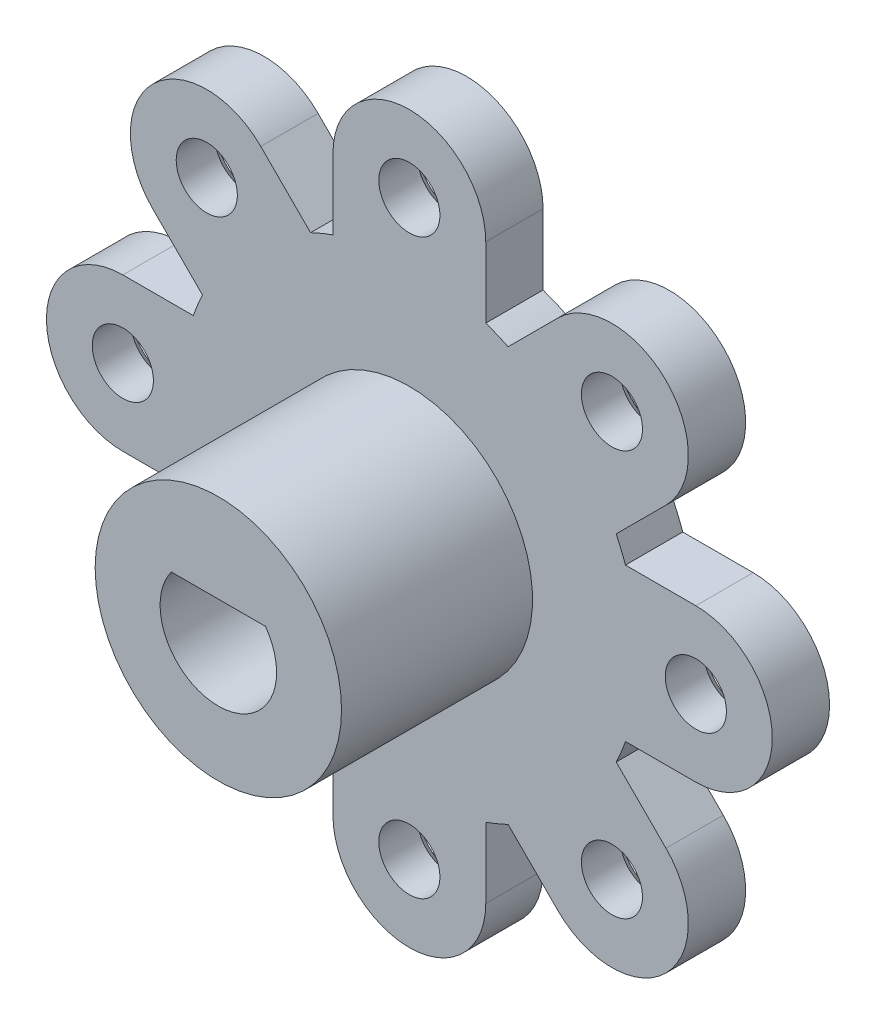
SolidWorks part; units mm, degrees
ref_plane "Front Plane" through (0, 0, 0) normal (0, 0, 1) x (1, 0, 0)
ref_plane "Top Plane" through (0, 0, 0) normal (0, 1, 0) x (1, 0, 0)
ref_plane "Right Plane" through (0, 0, 0) normal (1, 0, 0) x (0, 0, -1)
ref_axis "Axe1" through (0, 0, 11.8837) along (0, 0, -1)
sketch "Esquisse1" plane through (0, 0, 0) normal (0, 0, 1) x (1, 0, 0)
  line L0 (11.3137, 4) -> (15, 4)
  line L1 (11.3137, -4) -> (15, -4)
  line L2 (0, 0) -> (11.0866, 4.5922)
  line L3 (0, 0) -> (11.0866, -4.5922)
  line L4 (0, 0) -> (15, 0) construction
  arc A0 (11.0866, 4.5922) -> (11.3137, 4) centre (0, 0) cw
  arc A1 (11.0866, -4.5922) -> (11.3137, -4) centre (0, 0) ccw
  arc A2 (15, -4) -> (15, 4) centre (15, 0) ccw
  dimension "D1" = 12
  dimension "D2" = 8
  dimension "D3" = 15
  dimension "D4" = 22.5
  dimension "D5" = 22.5
extrude "Main" add sketch "Esquisse1" along normal blind 3
pattern_circular "Répétition circulaire1" count 8 every 45 about axis through (0, 0, 11.8837) along (0, 0, -1) of "Main"
sketch "Esquisse2" plane through (0, 0, 3) normal (0, 0, 1) x (1, 0, 0)
  circle A0 centre (0, 0) radius 3.05
  circle A1 centre (0, 0) radius 6.45
  dimension "D1" = 6.1
  dimension "D2" = 12.9
extrude "MotorLink" add sketch "Esquisse2" along normal blind 10
sketch "Esquisse3" plane through (0, 0, 3) normal (0, 0, 1) x (1, 0, 0)
  line L0 (-2.4622, 1.8) -> (2.4622, 1.8)
  circle A0 centre (0, 0) radius 3.05 construction
  arc A1 (2.4622, 1.8) -> (-2.4622, 1.8) centre (0, 0) ccw
  dimension "D1" = 1.8
extrude "Meplat" add sketch "Esquisse3" along normal blind 10
sketch "Esquisse4" plane through (0, 0, 3) normal (0, 0, 1) x (1, 0, 0)
  circle A0 centre (0, 0) radius 3.05
  circle A1 centre (0, 0) radius 3.05 construction
extrude "Hole" cut sketch "Esquisse4" against normal through all
sketch "Esquisse5" plane through (0, 0, 0) normal (0, 0, -1) x (-1, 0, 0)
  circle A0 centre (0, 0) radius 3.05
  circle A1 centre (0, 0) radius 4
  circle A2 centre (0, 0) radius 3.05 construction
  dimension "D1" = 8
extrude "RollingBearingLink" add sketch "Esquisse5" along normal blind 7
sketch "Esquisse6" plane through (0, 0, 0) normal (0, 0, -1) x (-1, 0, 0)
  circle A0 centre (0, 0) radius 5
  circle A1 centre (0, 0) radius 4
  circle A2 centre (0, 0) radius 4 construction
  dimension "D1" = 10
extrude "RollingBearLink2" add sketch "Esquisse6" along normal blind 0.5
hole_wizard "Fraisage pour vis à tête fraisée (100) #01" positions "Esquisse9" profile "Esquisse10" countersink size "#0" standard "Ansi Inch" end condition through all
sketch "Esquisse9" plane through (0, 0, 0) normal (0, 0, -1) x (-1, 0, 0)
  arc A1 (15, -4) -> (15, 4) centre (15, 0) ccw construction
  point P0 (15, 0)
sketch "Esquisse10" plane through (-15, 0, 0) normal (1, 0, 0) x (0, 1, 0)
  line L0 (0, 0) -> (0, 13)
  line L1 (0, 13) -> (1.6, 13)
  line L2 (1.6, 13) -> (1.6, 0.965)
  line L3 (1.6, 0.965) -> (2.75, 0)
  line L5 (2.75, 0) -> (0, 0)
  line L6 (-1.6, 0.965) -> (-2.75, 0) construction
  line L11 (0, -6.35) -> (0, 107.95) construction
  dimension "Diamètre du perçage jusqu'au prochain" = 3.2
  dimension "Profondeur du perçage jusqu'au prochain" = 13
  dimension "Diamètre du fraisage entrant" = 5.5
  dimension "Angle du fraisage entrant" = 100
pattern_circular "Répétition circulaire2" count 8 every 45 about axis through (0, 0, 11.8837) along (0, 0, -1) of "Fraisage pour vis à tête fraisée (100) #01"
